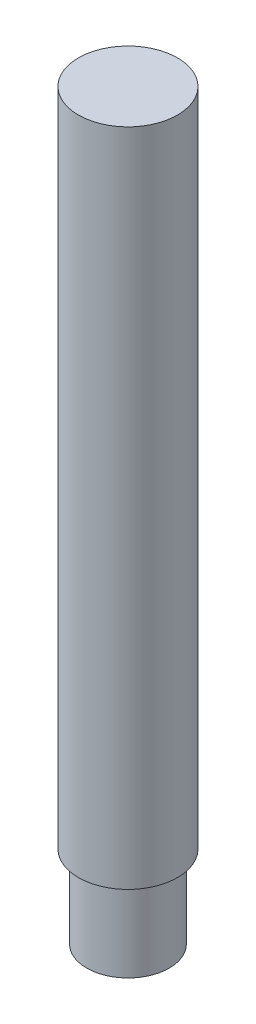
SolidWorks part; units mm, degrees
material "Plain Carbon Steel"
ref_plane "Front Plane" through (0, 0, 0) normal (0, 0, 1) x (1, 0, 0)
ref_plane "Top Plane" through (0, 0, 0) normal (0, 1, 0) x (1, 0, 0)
ref_plane "Right Plane" through (0, 0, 0) normal (1, 0, 0) x (0, 0, -1)
sketch "Sketch1" plane through (0, 0, 0) normal (0, 1, 0) x (1, 0, 0)
  circle A0 centre (0, 0) radius 3
  circle A1 centre (0, 0) radius 2.5
  dimension "D1" = 5
  dimension "D2" = 6
extrude "Boss-Extrude1" add sketch "Sketch1" along normal blind 5 contours A1 region at (0, 0, 0)
extrude "Boss-Extrude2" add sketch "Sketch1<4>" along normal blind 40 from surface contours A0 starting at face at (0, 5, 2.5)
sketch "Sketch1<4>" plane through (0, 0, 0) normal (0, 1, 0) x (1, 0, 0) same geometry as "Sketch1"
